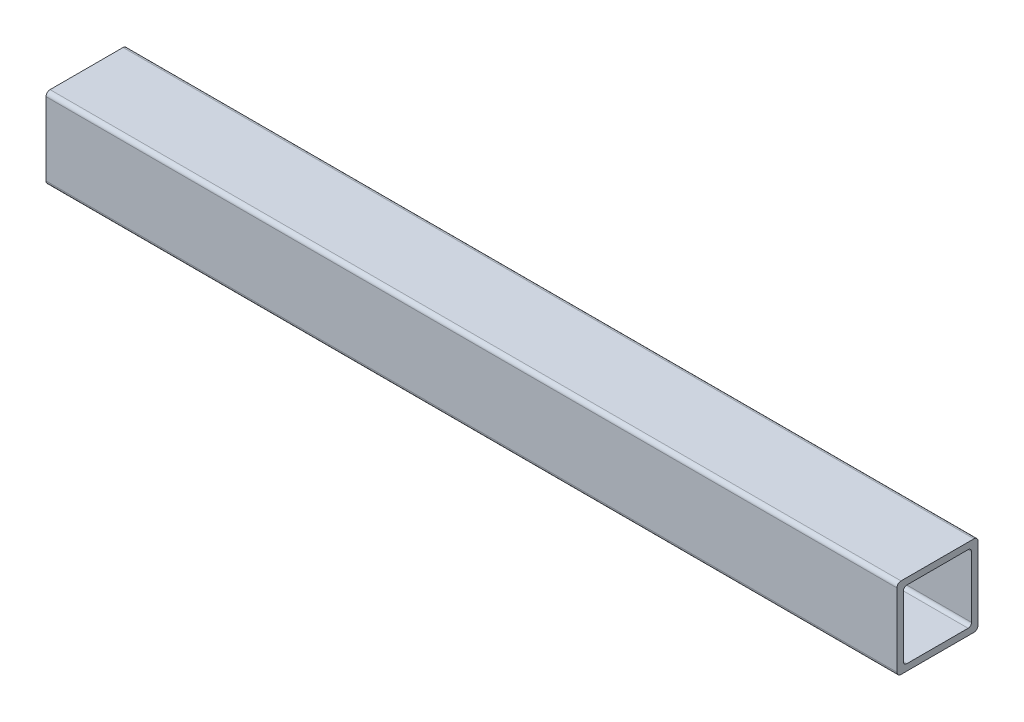
SolidWorks part; units mm, degrees
material "ASTM A36 Steel"
ref_plane "Front" through (0, 0, 0) normal (0, 0, 1) x (1, 0, 0)
ref_plane "Top" through (0, 0, 0) normal (0, 1, 0) x (1, 0, 0)
ref_plane "Right" through (0, 0, 0) normal (1, 0, 0) x (0, 0, -1)
sketch "Sketch1" plane through (0, 0, 0) normal (1, 0, 0) x (0, 0, -1)
  line L0 (-16.002, 0) -> (-19.05, 0) construction
  line L1 (17.145, -19.05) -> (-17.145, -19.05) construction
  line L2 (19.05, -17.145) -> (19.05, 17.145) construction
  line L3 (17.145, 19.05) -> (-17.145, 19.05) construction
  line L4 (-19.05, -17.145) -> (-19.05, 17.145) construction
  line L5 (19.05, -19.05) -> (-19.05, 19.05) construction
  line L6 (19.05, 19.05) -> (-19.05, -19.05) construction
  line L7 (14.4018, 16.002) -> (-14.4018, 16.002) construction
  line L8 (16.002, 14.4018) -> (16.002, -14.4018) construction
  line L9 (14.4018, -16.002) -> (-14.4018, -16.002) construction
  line L10 (-16.002, 14.4018) -> (-16.002, -14.4018) construction
  line L11 (16.002, 16.002) -> (-16.002, -16.002) construction
  line L12 (16.002, -16.002) -> (-16.002, 16.002) construction
  line L13 (0, -16.002) -> (0, -19.05) construction
  line L14 (16.002, -14.4018) -> (16.002, -19.05) construction
  line L15 (16.002, 0) -> (19.05, 0) construction
  line L16 (16.002, -19.05) -> (19.05, -19.05) construction
  arc A0 (-14.4018, -16.002) -> (-16.002, -14.4018) centre (-14.4018, -14.4018) cw construction
  arc A1 (16.002, -14.4018) -> (14.4018, -16.002) centre (14.4018, -14.4018) cw construction
  arc A2 (14.4018, 16.002) -> (16.002, 14.4018) centre (14.4018, 14.4018) cw construction
  arc A3 (-14.4018, 16.002) -> (-16.002, 14.4018) centre (-14.4018, 14.4018) ccw construction
  arc A4 (17.145, -19.05) -> (19.05, -17.145) centre (17.145, -17.145) ccw construction
  arc A5 (19.05, 17.145) -> (17.145, 19.05) centre (17.145, 17.145) ccw construction
  arc A6 (-17.145, 19.05) -> (-19.05, 17.145) centre (-17.145, 17.145) ccw construction
  arc A7 (-17.145, -19.05) -> (-19.05, -17.145) centre (-17.145, -17.145) cw construction
  point P0 (0, 0)
  point P6 (0, 0)
  dimension "D2" = 1.6002
  dimension "D3" = 1.905
  dimension "Outside Width" = 38.1
  dimension "Ouside Height" = 38.1
  dimension "Inside Height" = 32.004
  dimension "Wall Thickness" = 3.048
sketch "Sketch2" plane through (0, 0, 0) normal (0, 0, 1) x (1, 0, 0)
  line L0 (-200, 0) -> (200, 0) construction
  point P3 (-164.948, 0)
  point P4 (164.948, 0)
  dimension "Length" = 400
  dimension "D1" = 35.052
  dimension "D2" = 35.052
sketch "Sketch4" plane through (0, 0, 0) normal (1, 0, 0) x (0, 0, -1)
  line L8 (19.05, -17.145) -> (19.05, 17.145)
  line L9 (17.145, 19.05) -> (-17.145, 19.05)
  line L10 (-19.05, -17.145) -> (-19.05, 17.145)
  line L11 (17.145, -19.05) -> (-17.145, -19.05)
  line L12 (16.002, 14.4018) -> (16.002, -14.4018)
  line L13 (14.4018, -16.002) -> (-14.4018, -16.002)
  line L14 (-16.002, 14.4018) -> (-16.002, -14.4018)
  line L15 (14.4018, 16.002) -> (-14.4018, 16.002)
  arc A8 (19.05, 17.145) -> (17.145, 19.05) centre (17.145, 17.145) ccw
  arc A9 (-17.145, 19.05) -> (-19.05, 17.145) centre (-17.145, 17.145) ccw
  arc A10 (-19.05, -17.145) -> (-17.145, -19.05) centre (-17.145, -17.145) ccw
  arc A11 (17.145, -19.05) -> (19.05, -17.145) centre (17.145, -17.145) ccw
  arc A12 (14.4018, -16.002) -> (16.002, -14.4018) centre (14.4018, -14.4018) ccw
  arc A13 (-16.002, -14.4018) -> (-14.4018, -16.002) centre (-14.4018, -14.4018) ccw
  arc A14 (-14.4018, 16.002) -> (-16.002, 14.4018) centre (-14.4018, 14.4018) ccw
  arc A15 (16.002, 14.4018) -> (14.4018, 16.002) centre (14.4018, 14.4018) ccw
extrude "Boss-Extrude1" add sketch "Sketch4" along normal up to vertex (-200 mm away) and the other way up to vertex (-200 mm away) up to point (-200, 0, 0) other way up to point (200, 0, 0)
equation "\"D3@Sketch1\"=\"Outside Width@Sketch1\"*.05"
equation "\"D2@Sketch1\" = \"Inside Height@Sketch1\" * .05"
equation "\"D1@Sketch2\"=\"Outside Width@Sketch1\"-\"Wall Thickness@Sketch1\""
equation "\"D2@Sketch2\"=\"D1@Sketch2\""
